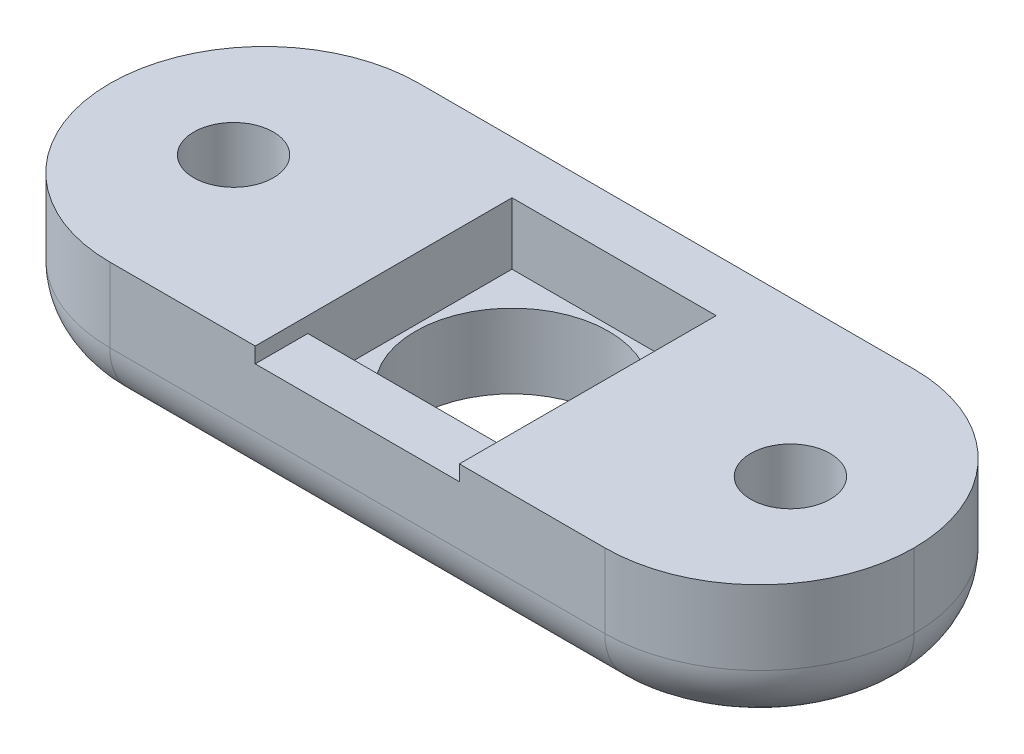
SolidWorks part; units mm, degrees
ref_plane "Front Plane" through (0, 0, 0) normal (0, 0, 1) x (1, 0, 0)
ref_plane "Top Plane" through (0, 0, 0) normal (0, 1, 0) x (1, 0, 0)
ref_plane "Right Plane" through (0, 0, 0) normal (1, 0, 0) x (0, 0, -1)
sketch "Sketch1" plane through (0, 0, 0) normal (0, 1, 0) x (1, 0, 0)
  line L1 (1.1641, 10.6991) -> (-31.8559, 10.6991)
  line L2 (1.1641, 10.6991) -> (1.1641, -2.0009)
  line L3 (1.1641, -2.0009) -> (-31.8559, -2.0009)
  line L4 (-31.8559, 10.6991) -> (-31.8559, -2.0009)
  line L5 (1.1641, 10.6991) -> (-31.8559, -2.0009) construction
  line L6 (1.1641, -2.0009) -> (-31.8559, 10.6991) construction
  circle A0 centre (-15.3459, 4.3491) radius 3.9688
  dimension "D1" = 7.9375
  dimension "D2" = 12.7
  dimension "D3" = 33.02
extrude "Boss-Extrude1" add sketch "Sketch1" along normal blind 5.588
sketch "Sketch2" plane through (0, 5.588, 0) normal (0, 1, 0) x (1, 0, 0)
  line L1 (-11.1549, 8.5401) -> (-19.5369, 8.5401)
  line L2 (-11.1549, 8.5401) -> (-11.1549, 0.1581)
  line L3 (-11.1549, 0.1581) -> (-19.5369, 0.1581)
  line L4 (-19.5369, 8.5401) -> (-19.5369, 0.1581)
  line L5 (-11.1549, 8.5401) -> (-19.5369, 0.1581) construction
  line L6 (-11.1549, 0.1581) -> (-19.5369, 8.5401) construction
  point P0 (-15.3459, 4.3491)
  dimension "D1" = 8.382
  dimension "D2" = 8.382
extrude "Cut-Extrude1" cut sketch "Sketch2" against normal blind 2.54
hole_wizard "#4 Clearance Hole1" positions "Sketch6" profile "Sketch5" hole size "#4" standard "ANSI Inch"
sketch "Sketch6" plane through (0, 0, 0) normal (0, -1, 0) x (-1, 0, 0)
  line L0 (15.3459, 10.6991) -> (15.3459, -3.7399) construction
  line L1 (-1.1641, 10.6991) -> (31.8559, 10.6991) construction
  line L3 (-1.1641, 4.3491) -> (31.8559, 4.3491) construction
  line L4 (-1.1641, -2.0009) -> (-1.1641, 10.6991) construction
  line L5 (31.8559, 10.6991) -> (31.8559, -2.0009) construction
  point P0 (3.9159, 4.3491)
  point P2 (26.7759, 4.3491)
  dimension "D1" = 22.86
sketch "Sketch5" plane through (-3.9159, 0, -4.3491) normal (1, 0, 0) x (0, 0, -1)
  line L0 (0, 0) -> (0, 13.6806)
  line L1 (0, 13.6806) -> (1.6319, 12.7)
  line L2 (1.6319, 12.7) -> (1.6319, 0)
  line L5 (1.6319, 0) -> (0, 0)
  line L10 (0, 13.6806) -> (-1.632, 12.7) construction
  line L11 (0, -6.35) -> (0, 107.95) construction
  dimension "Hole Dia." = 3.2639
  dimension "Hole Depth" = 12.7
  dimension "Drill Angle" = 118
fillet "Fillet1" radius 6.35 4 edges at (-31.8559, 2.794, 2.0009) (-31.8559, 2.794, -10.6991) (1.1641, 2.794, -10.6991) (1.1641, 2.794, 2.0009)
sketch "Sketch7" plane through (0, 5.588, 0) normal (0, 1, 0) x (1, 0, 0)
  line L0 (-25.5059, -2.0009) -> (-5.1859, -2.0009) construction
  line L1 (-11.1549, 0.1581) -> (-19.5369, 0.1581)
  line L2 (-11.1549, 0.1581) -> (-11.1549, -2.0009)
  line L3 (-11.1549, -2.0009) -> (-19.5369, -2.0009)
  line L4 (-19.5369, 0.1581) -> (-19.5369, -2.0009)
  line L5 (-19.5369, 8.5401) -> (-19.5369, 0.1581) construction
extrude "Cut-Extrude2" cut sketch "Sketch7" against normal blind 0.635
sketch "Sketch9" plane through (0, 0, 0) normal (0, -1, 0) x (1, 0, 0)
  circle A0 centre (-3.9159, -4.3491) radius 2.54
  circle A1 centre (-26.7759, -4.3491) radius 2.54
  dimension "D1" = 5.08
  dimension "D2" = 5.08
extrude "Cut-Extrude3" cut sketch "Sketch9" against normal blind 3.175
fillet "Fillet3" radius 2.54 6 edges at (-29.9961, 0, 0.141) (-15.3459, 0, 2.0009) (-0.6958, 0, 0.141) (-0.6958, 0, -8.8393) (-15.3459, 0, -10.6991) (-29.9961, 0, -8.8393)
